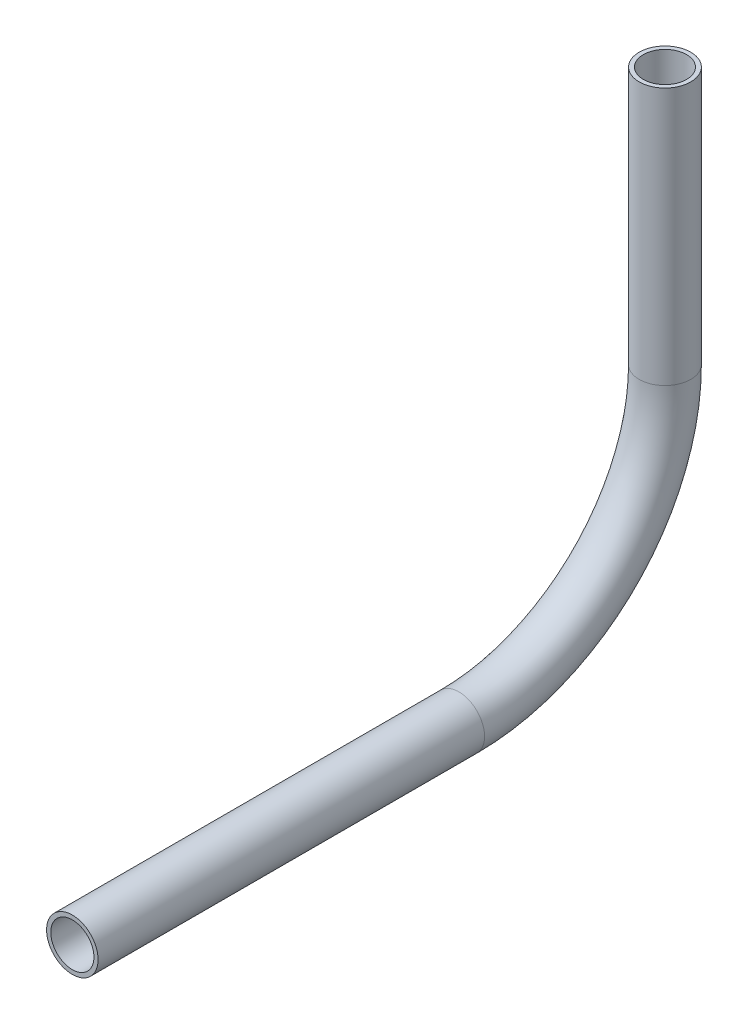
SolidWorks part; units mm, degrees
ref_plane "Front" through (0, 0, 0) normal (0, 0, 1) x (1, 0, 0)
ref_plane "Top" through (0, 0, 0) normal (0, 1, 0) x (1, 0, 0)
ref_plane "Right" through (0, 0, 0) normal (1, 0, 0) x (0, 0, -1)
sketch "Sketch1" plane through (0, 0, 0) normal (1, 0, 0) x (0, 0, -1)
  line L13 (60, 0) -> (0, 0)
  line L14 (92, 32) -> (92, 72)
  arc A0 (60, 0) -> (92, 32) centre (60, 32) ccw
  dimension "D4" = 60
  dimension "D1" = 40
  dimension "D5" = 32
sketch "Sketch2" plane through (0, 0, 0) normal (0, 0, 1) x (1, 0, 0)
  circle A0 centre (0, 0) radius 4
  dimension "D1" = 8
sweep "Sweep1" add profiles "Sketch2" path "Sketch1"
sketch "Sketch3" plane through (0, 0, 0) normal (0, 0, 1) x (1, 0, 0)
  circle A0 centre (0, 0) radius 3.35
  dimension "D1" = 6.7
sweep "Cut-Sweep1" cut profiles "Sketch3" path "Sketch1<4>"
sketch "Sketch1<4>" plane through (0, 0, 0) normal (1, 0, 0) x (0, 0, -1) same geometry as "Sketch1"
